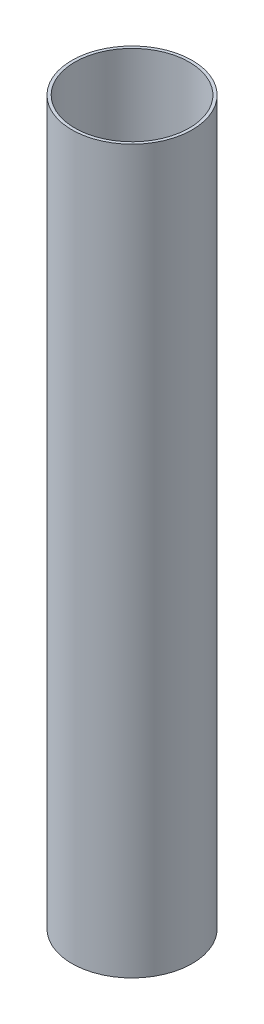
SolidWorks part; units mm, degrees
material "S-Glass Fiber"
ref_plane "Front Plane" through (0, 0, 0) normal (0, 0, 1) x (1, 0, 0)
ref_plane "Top Plane" through (0, 0, 0) normal (0, 1, 0) x (1, 0, 0)
ref_plane "Right Plane" through (0, 0, 0) normal (1, 0, 0) x (0, 0, -1)
sketch "Sketch1" plane through (0, 0, 0) normal (0, 1, 0) x (1, 0, 0)
  circle A0 centre (0, 0) radius 24.1554
  circle A1 centre (0, 0) radius 25.4
  dimension "D1" = 50.8
  dimension "D2" = 48.3108
extrude "Boss-Extrude1" add sketch "Sketch1" along normal blind 304.8
